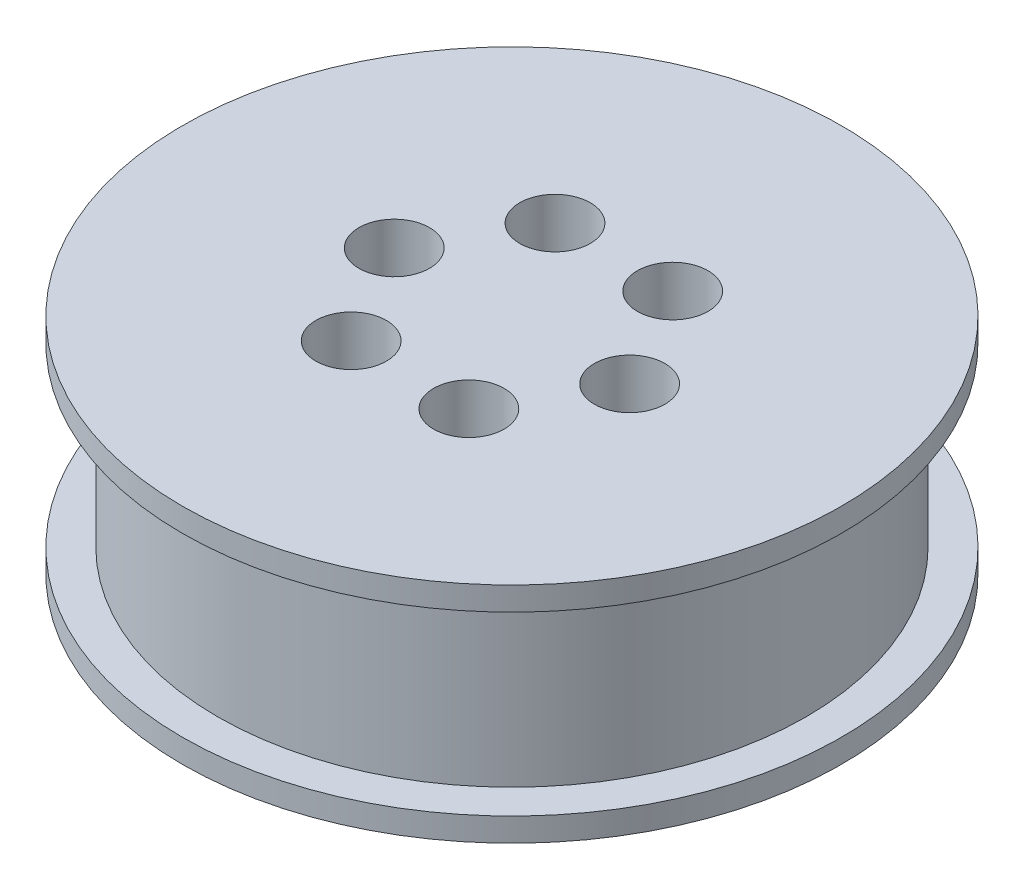
SolidWorks part; units mm, degrees
material "PETG"
ref_plane "Front Plane" through (0, 0, 0) normal (0, 0, 1) x (1, 0, 0)
ref_plane "Top Plane" through (0, 0, 0) normal (0, 1, 0) x (1, 0, 0)
ref_plane "Right Plane" through (0, 0, 0) normal (1, 0, 0) x (0, 0, -1)
sketch "Sketch1" plane through (0, 0, 0) normal (0, 1, 0) x (1, 0, 0)
  circle A0 centre (0, 0) radius 25
  dimension "D1" = 50
extrude "Boss-Extrude1" add sketch "Sketch1" along normal mid plane 15
sketch "Sketch2" plane through (0, 7.5, 0) normal (0, 1, 0) x (1, 0, 0)
  circle A0 centre (0, 0) radius 28
  dimension "D1" = 56
extrude "Boss-Extrude2" add sketch "Sketch2" along normal blind 2
mirror "Mirror1" about plane through (0, 0, 0) normal (0, 1, 0) of "Boss-Extrude2"
sketch "Sketch3" plane through (0, 9.5, 0) normal (0, 1, 0) x (1, 0, 0)
  line L0 (0, 0) -> (10, 0) construction
  circle A0 centre (10, 0) radius 1.7
  circle A1 centre (5, -8.6603) radius 1.7
  circle A2 centre (-5, -8.6603) radius 1.7
  circle A3 centre (-10, 0) radius 1.7
  circle A4 centre (-5, 8.6603) radius 1.7
  circle A5 centre (5, 8.6603) radius 1.7
  dimension "D1" = 10
  dimension "D2" = 3.4
  dimension "D3" = 6
extrude "Cut-Extrude1" cut sketch "Sketch3" against normal through all
sketch "Sketch4" plane through (0, 9.5, 0) normal (0, 1, 0) x (1, 0, 0)
  line L0 (0, 0) -> (5, -8.6603) construction
  circle A0 centre (5, -8.6603) radius 3
  circle A1 centre (-5, -8.6603) radius 3
  circle A2 centre (-10, 0) radius 3
  circle A3 centre (-5, 8.6603) radius 3
  circle A4 centre (5, 8.6603) radius 3
  circle A5 centre (10, 0) radius 3
  point P3 (0, 0)
  dimension "D1" = 6
  dimension "D2" = 6
extrude "Cut-Extrude2" cut sketch "Sketch4" against normal blind 5
